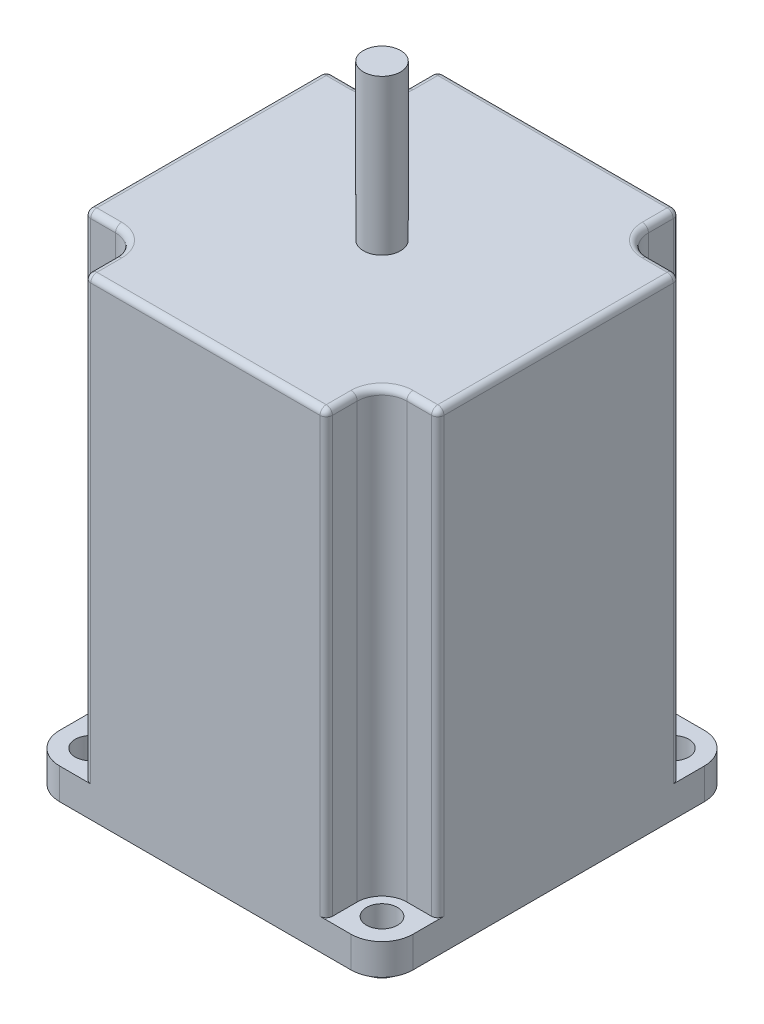
SolidWorks part; units mm, degrees
note: '?' marks a value the reader was unsure of.
material "1023 Carbon Steel Sheet (SS)"
ref_plane "Front" through (0, 0, 0) normal (0, 0, 1) x (1, 0, 0)
ref_plane "Top" through (0, 0, 0) normal (0, 1, 0) x (1, 0, 0)
ref_plane "Right" through (0, 0, 0) normal (1, 0, 0) x (0, 0, -1)
ref_axis "Axis1" through (-84.4107, 0, 0) along (1, 0, 0)?
ref_axis "Axis2" through (0, 64.3378, 0) along (0, -1, 0)?
ref_axis "Axis3" through (0, 0, -102.329) along (0, 0, 1)?
sketch "Sketch1" plane through (0, 0, 0) normal (0, 1, 0) x (1, 0, 0)
  line L1 (-28.5, -28.5) -> (28.5, -28.5)
  line L2 (-28.5, -28.5) -> (-28.5, 28.5)
  line L3 (-28.5, 28.5) -> (28.5, 28.5)
  line L4 (28.5, -28.5) -> (28.5, 28.5)
  line L5 (-28.5, -28.5) -> (28.5, 28.5) construction
  line L6 (-28.5, 28.5) -> (28.5, -28.5) construction
  point P0 (0, 0)
  dimension "D1" = 57
  dimension "D2" = 57
extrude "Extrude1" add sketch "Sketch1" along normal blind 76
hole_wizard "Ø5.0 (5) Diameter Hole1" positions "Sketch5" profile "Sketch4" hole size "Ø5.0" standard "ISO" end condition through all
sketch "Sketch5" plane through (0, 0, 0) normal (0, -1, 0) x (1, 0, 0)
  line L0 (-28.5, 28.5) -> (28.5, -28.5) construction
  line L3 (28.5, 28.5) -> (-28.5, -28.5) construction
  point P0 (-23.5, 23.5)
  point P1 (23.5, 23.5)
  point P3 (23.5, -23.5)
  point P5 (-23.5, -23.5)
  dimension "D1" = 47
  dimension "D2" = 47
sketch "Sketch4" plane through (-23.5, 0, 23.5) normal (1, 0, 0) x (0, 0, -1)
  line L0 (0, 0) -> (0, 76)
  line L1 (0, 76) -> (2.5, 76)
  line L2 (2.5, 76) -> (2.5, 0)
  line L5 (2.5, 0) -> (0, 0)
  line L11 (0, -6.35) -> (0, 107.95) construction
  dimension "Thru Hole Dia." = 5
  dimension "Thru Hole Depth" = 76
sketch "Sketch6" plane through (0, 76, 0) normal (0, 1, 0) x (1, 0, 0)
  line L0 (-19.5, 23.5) -> (-19.5, 32.5117)
  line L1 (-19.5, 32.5117) -> (-33.9089, 32.5117)
  line L2 (-33.9089, 32.5117) -> (-33.9089, 19.5)
  line L3 (-33.9089, 19.5) -> (-23.5, 19.5)
  line L4 (19.5, 23.5) -> (19.5, 36.4716)
  line L5 (19.5, 36.4716) -> (41.1684, 36.4716)
  line L6 (41.1684, 36.4716) -> (41.1684, 19.5)
  line L7 (41.1684, 19.5) -> (23.5, 19.5)
  line L8 (23.5, -19.5) -> (44.2522, -19.5)
  line L9 (44.2522, -19.5) -> (44.2522, -40.0504)
  line L10 (44.2522, -40.0504) -> (19.5, -40.0504)
  line L11 (19.5, -40.0504) -> (19.5, -23.5)
  line L12 (-23.5, -19.5) -> (-37.6708, -19.5)
  line L13 (-37.6708, -19.5) -> (-37.6708, -37.8282)
  line L14 (-37.6708, -37.8282) -> (-19.5, -37.8282)
  line L15 (-19.5, -37.8282) -> (-19.5, -23.5)
  circle A0 centre (-23.5, 23.5) radius 4
  circle A1 centre (23.5, 23.5) radius 4
  circle A2 centre (23.5, -23.5) radius 4
  circle A3 centre (-23.5, -23.5) radius 4
  circle M1 centre (-23.5, -23.5) radius 2.5
  circle M2 centre (23.5, -23.5) radius 2.5
  circle M3 centre (23.5, 23.5) radius 2.5
  circle M4 centre (-23.5, 23.5) radius 2.5
  line M5 (28.5, -28.5) -> (28.5, 28.5)
  line M6 (28.5, 28.5) -> (-28.5, 28.5)
  line M7 (-28.5, 28.5) -> (-28.5, -28.5)
  line M8 (-28.5, -28.5) -> (28.5, -28.5)
  dimension "D1" = 8
  dimension "D2" = 8
  dimension "D3" = 8
  dimension "D4" = 8
extrude "Extrude4" cut sketch "Sketch6" against normal blind 71 contours L2 L3 L0 L1 M7 M6 | A0 L0 L3 M6 M7 | A0 M4 | L7 L6 L5 L4 M6 M5 | A1 L7 L4 M5 M6 | A1 M3 | A2 M2 | A2 L11 L8 M8 M5 | L11 L10 L9 L8 M5 M8 | L14 L15 L12 L13 M8 M7 | A3 L12 L15 M7 M8 | A3 M1
fillet "Fillet1" radius 5 4 edges at (-28.5, 2.5, 28.5) (28.5, 2.5, 28.5) (28.5, 2.5, -28.5) (-28.5, 2.5, -28.5)
sketch "Sketch7" plane through (0, 76, 0) normal (0, 1, 0) x (1, 0, 0)
  circle A0 centre (0, 0) radius 3
  dimension "D1" = 6
extrude "Extrude5" add sketch "Sketch7" along normal blind 25 and the other way blind 101 separate body
sketch "Sketch8" plane through (0, 0, 0) normal (0, -1, 0) x (1, 0, 0)
  circle A0 centre (0, 0) radius 15
  dimension "D1" = 30
extrude "Extrude6" add sketch "Sketch8" along normal blind 3
fillet "Fillet2" radius 1 24 edges at (-26, 76, 19.5) (-20.6716, 76, 20.6716) (-19.5, 76, 26) (0, 76, 28.5) (19.5, 76, 26) (20.6716, 76, 20.6716) (26, 76, 19.5) (28.5, 76, 0) (19.5, 76, -26) (26, 76, -19.5) (20.6716, 76, -20.6716) (-26, 76, -19.5) (-19.5, 76, -26) (-20.6716, 76, -20.6716) (0, 76, -28.5) (-28.5, 76, 0) (-19.5, 40.5, 28.5) (-28.5, 40.5, 19.5) (-28.5, 40.5, -19.5) (-19.5, 40.5, -28.5) (19.5, 40.5, -28.5) (28.5, 40.5, -19.5) (28.5, 40.5, 19.5) (19.5, 40.5, 28.5)
